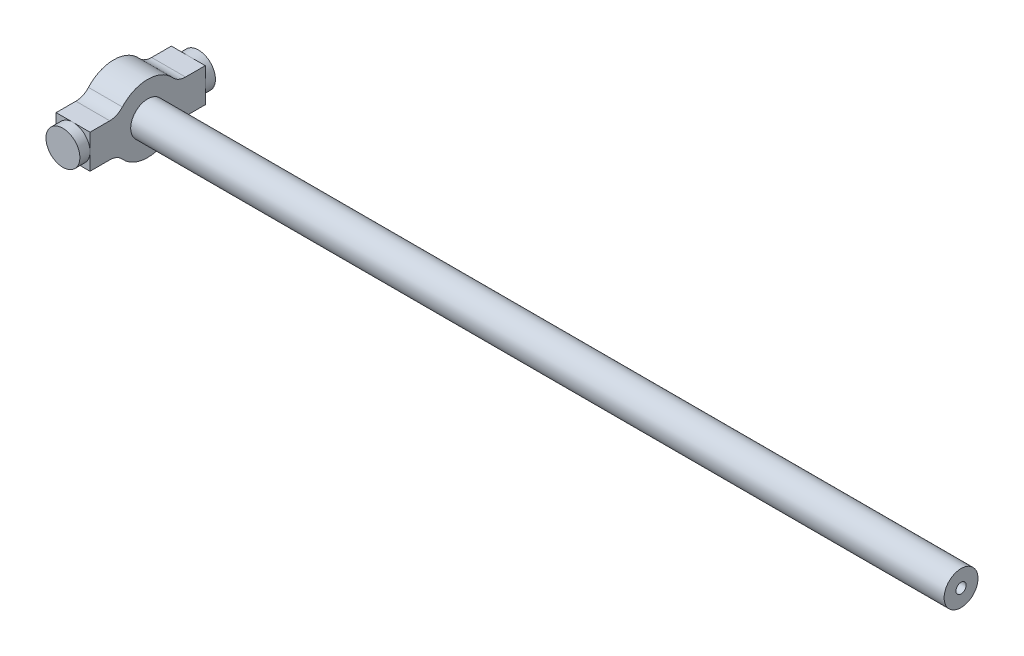
SolidWorks part; units mm, degrees
ref_plane "Front Plane" through (0, 0, 0) normal (0, 0, 1) x (1, 0, 0)
ref_plane "Top Plane" through (0, 0, 0) normal (0, 1, 0) x (1, 0, 0)
ref_plane "Right Plane" through (0, 0, 0) normal (1, 0, 0) x (0, 0, -1)
sketch "Primary Tube Sketch" plane through (0, 0, 0) normal (1, 0, 0) x (0, 0, -1)
  circle A1 centre (0, 0) radius 5
  dimension "D2" = 10
extrude "Primary Tube Extrude" add sketch "Primary Tube Sketch" along normal blind 250
sketch "Plunger Sketch" plane through (250, 0, 0) normal (1, 0, 0) x (0, 0, -1)
  circle A0 centre (0, 0) radius 1.5
  dimension "D1" = 3
extrude "Plunger Cut" cut sketch "Plunger Sketch" against normal blind 100
sketch "T Support Sketch" plane through (0, 0, 0) normal (-1, 0, 0) x (0, 0, 1)
  line L0 (8.6603, 5) -> (17, 5)
  line L1 (-17, 5) -> (-8.6603, 5)
  line L2 (-17, 5) -> (-17, -5)
  line L3 (-17, -5) -> (-8.6603, -5)
  line L4 (17, 5) -> (17, -5)
  line L5 (-17, 5) -> (17, -5) construction
  line L6 (-17, -5) -> (17, 5) construction
  line L7 (8.6603, -5) -> (17, -5)
  circle A0 centre (0, 0) radius 5 construction
  arc A1 (-8.6603, -5) -> (8.6603, -5) centre (0, 0) ccw
  arc A2 (8.6603, 5) -> (-8.6603, 5) centre (0, 0) ccw
  point P0 (0, 0)
  dimension "D2" = 20
  dimension "D1" = 34
extrude "T Support Extrude" add sketch "T Support Sketch" against normal blind 10 separate body
fillet "T Support Fillet" radius 5 4 edges at (5, -5, 8.6603) (5, -5, -8.6603) (5, 5, 8.6603) (5, 5, -8.6603)
sketch "Arm Pin Sketch" plane through (0, 0, 17) normal (0, 0, 1) x (1, 0, 0)
  line L0 (10, 5) -> (0, 5) construction
  line L1 (0, -5) -> (0, 5) construction
  circle A0 centre (5, 0) radius 5
  dimension "D1" = 10
extrude "Arm Pin Extrude 1" add sketch "Arm Pin Sketch" along normal blind 3 separate body
extrude "Arm Pin Extrude 2" add sketch "Arm Pin Sketch<2>" against normal blind 3 from surface separate body starting at face at (5, 0, -17)
sketch "Arm Pin Sketch<2>" plane through (0, 0, 17) normal (0, 0, 1) x (1, 0, 0) same geometry as "Arm Pin Sketch"
